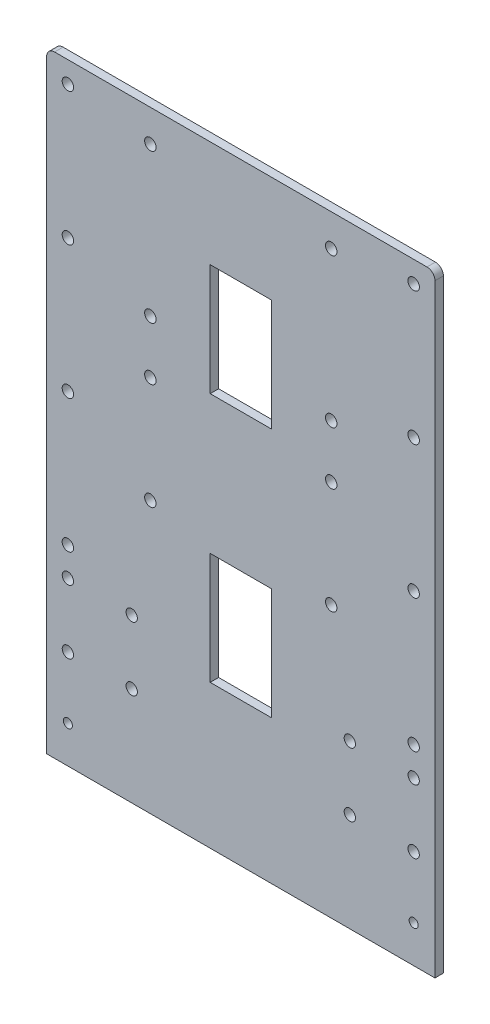
SolidWorks part; units mm, degrees
ref_plane "Front Plane" through (0, 0, 0) normal (0, 0, 1) x (1, 0, 0)
ref_plane "Top Plane" through (0, 0, 0) normal (0, 1, 0) x (1, 0, 0)
ref_plane "Right Plane" through (0, 0, 0) normal (1, 0, 0) x (0, 0, -1)
sketch "Sketch1" plane through (0, 0, 0) normal (0, 0, 1) x (1, 0, 0)
  line L0 (0, 115) -> (0, -115) construction
  line L1 (-73, -115) -> (73, -115)
  line L2 (-73, -115) -> (-73, 115)
  line L3 (-73, 115) -> (73, 115)
  line L4 (73, -115) -> (73, 115)
  line L5 (-73, -115) -> (73, 115) construction
  line L6 (-73, 115) -> (73, -115) construction
  line L7 (-53, -81.6804) -> (-53, -63.9214) construction
  line L10 (-65, -65.85) -> (-39.3402, -65.85) construction
  line L12 (-40, -115) -> (40, -115) construction
  line L13 (-40, -115) -> (-40, 115) construction
  line L14 (-40, 115) -> (40, 115) construction
  line L15 (40, -115) -> (40, 115) construction
  line L16 (-40, -115) -> (40, 115) construction
  line L17 (-40, 115) -> (40, -115) construction
  line L19 (-11.5, 33) -> (11.5, 33)
  line L20 (-11.5, 33) -> (-11.5, 75)
  line L21 (-11.5, 75) -> (11.5, 75)
  line L22 (11.5, 33) -> (11.5, 75)
  line L23 (-11.5, 33) -> (11.5, 75) construction
  line L24 (-11.5, 75) -> (11.5, 33) construction
  line L30 (-11.5, -61) -> (11.5, -61)
  line L31 (11.5, -19) -> (11.5, -61)
  line L32 (-11.5, -19) -> (11.5, -19)
  line L33 (-11.5, -19) -> (-11.5, -61)
  circle A11 centre (-65, -77.85) radius 2.125
  circle A12 centre (-41, -77.85) radius 2.125
  circle A13 centre (-41, -53.85) radius 2.125
  circle A14 centre (-65, -53.85) radius 2.125
  circle A15 centre (41, -77.85) radius 2.125
  circle A16 centre (65, -77.85) radius 2.125
  circle A17 centre (65, -53.85) radius 2.125
  circle A18 centre (41, -53.85) radius 2.125
  circle A20 centre (-65, -101.025) radius 1.7
  circle A21 centre (65, -101.025) radius 1.7
  circle A22 centre (-34, 103) radius 2.15
  circle A23 centre (-34, 47) radius 2.15
  circle A24 centre (34, 47) radius 2.15
  circle A25 centre (34, 103) radius 2.15
  circle A26 centre (-34, 27) radius 2.15
  circle A30 centre (-65, 107) radius 2.15
  circle A31 centre (-65, 57) radius 2.15
  circle A32 centre (-65, 7) radius 2.15
  circle A33 centre (-65, -43) radius 2.15
  circle A34 centre (65, -43) radius 2.15
  circle A35 centre (65, 7) radius 2.15
  circle A36 centre (65, 57) radius 2.15
  circle A37 centre (65, 107) radius 2.15
  circle A38 centre (-34, 7) radius 2.15 [skipped]
  circle A39 centre (-34, -13) radius 2.15
  circle A40 centre (34, -13) radius 2.15
  circle A41 centre (34, 27) radius 2.15
  point P0 (0, 0)
  point P11 (0, 0)
  point P19 (0, 75)
  point P72 (0, 54)
  dimension "D3" = 4.3
  dimension "D4" = 6
  dimension "D5" = 12
  dimension "D6" = 80
  dimension "D8" = 4.25
  dimension "D9" = 8
  dimension "D10" = 37.15
  dimension "D12" = 3
  dimension "D14" = 4.3
  dimension "D19" = 3.4
  dimension "D7" = 2
  dimension "D1" = 146
  dimension "D2" = 230
  dimension "D11" = 12
  dimension "D13" = 12
  dimension "D15" = 8
  dimension "D16" = 8
  dimension "D17" = 4
  dimension "D18" = 20
  dimension "D20" = 8
  dimension "D21" = 13.975
  dimension "D22" = 2
  dimension "D23" = 23
  dimension "D24" = 42
  dimension "D25" = 40
  dimension "D26" = 134
extrude "Boss-Extrude1" add sketch "Sketch1" along normal blind 3.175
fillet "Fillet1" radius 3 2 edges at (73, 115, 1.5875) (-73, 115, 1.5875)
